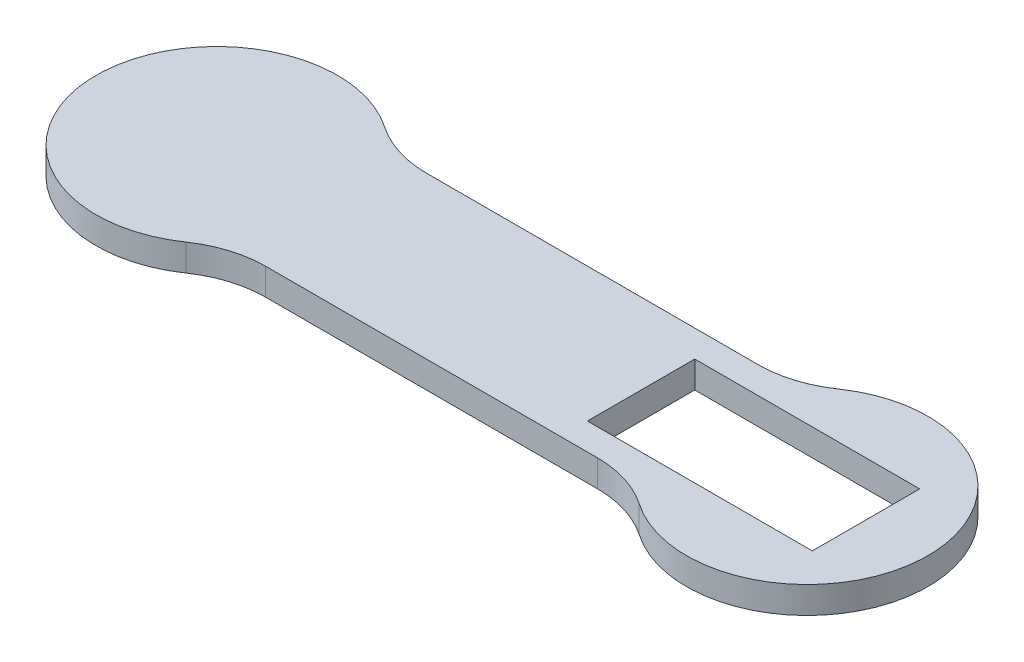
SolidWorks part; units mm, degrees
material "ABS"
ref_plane "Front Plane" through (0, 0, 0) normal (0, 0, 1) x (1, 0, 0)
ref_plane "Top Plane" through (0, 0, 0) normal (0, 1, 0) x (1, 0, 0)
ref_plane "Right Plane" through (0, 0, 0) normal (1, 0, 0) x (0, 0, -1)
other "Center of Mass"
sketch "Sketch2" plane through (0, 0, 0) normal (0, 1, 0) x (1, 0, 0)
  line L0 (0, 0) -> (136.4639, 0) construction
  line L1 (24.1091, 15) -> (85.8909, 15)
  line L3 (24.1091, -15) -> (85.8909, -15)
  line L5 (137.9207, 0) -> (181.8456, 0) construction
  arc A0 (12.7637, 18.5294) -> (12.7637, -18.5294) centre (0, 0) ccw
  arc A1 (97.2363, -18.5294) -> (97.2363, 18.5294) centre (110, 0) ccw
  arc A2 (97.2363, -18.5294) -> (85.8909, -15) centre (85.8909, -35) ccw
  arc A3 (97.2363, 18.5294) -> (85.8909, 15) centre (85.8909, 35) cw
  arc A4 (24.1091, -15) -> (12.7637, -18.5294) centre (24.1091, -35) ccw
  arc A5 (24.1091, 15) -> (12.7637, 18.5294) centre (24.1091, 35) cw
  point P16 (16.7705, -15)
  point P19 (16.7705, 15)
  dimension "D1" = 45
  dimension "D4" = 45
  dimension "D5" = 20
  dimension "D2" = 30
  dimension "D3" = 110
extrude "Boss-Extrude1" add sketch "Sketch2" along normal blind 5
sketch "Sketch3" plane through (0, 5, 0) normal (0, 1, 0) x (1, 0, 0)
  line L0 (0, 0) -> (125.1104, 0) construction
  line L1 (125.1104, 0) -> (159.77, 0) construction
  line L3 (73, -10) -> (127, -10)
  line L4 (73, -10) -> (73, 10)
  line L5 (73, 10) -> (127, 10)
  line L6 (127, -10) -> (127, 10)
  line L7 (73, -10) -> (127, 10) construction
  line L8 (73, 10) -> (127, -10) construction
  line L9 (79.05, -10.5) -> (120.95, -10.5)
  line L10 (79.05, -10.5) -> (79.05, 10.5)
  line L11 (79.05, 10.5) -> (120.95, 10.5)
  line L12 (120.95, -10.5) -> (120.95, 10.5)
  line L13 (79.05, -10.5) -> (120.95, 10.5) construction
  line L14 (79.05, 10.5) -> (120.95, -10.5) construction
  arc A0 (97.2363, -18.5294) -> (97.2363, 18.5294) centre (110, 0) ccw construction
  point P4 (100, 0)
  point P12 (100, 0)
  dimension "D2" = 17
  dimension "D1" = 20
  dimension "D3" = 54
  dimension "D4" = 41.9
  dimension "D5" = 21
extrude "Cut-Extrude1" cut sketch "Sketch3" against normal through all contours L3 L12 L5 L10 region at (100, 5, 0)
